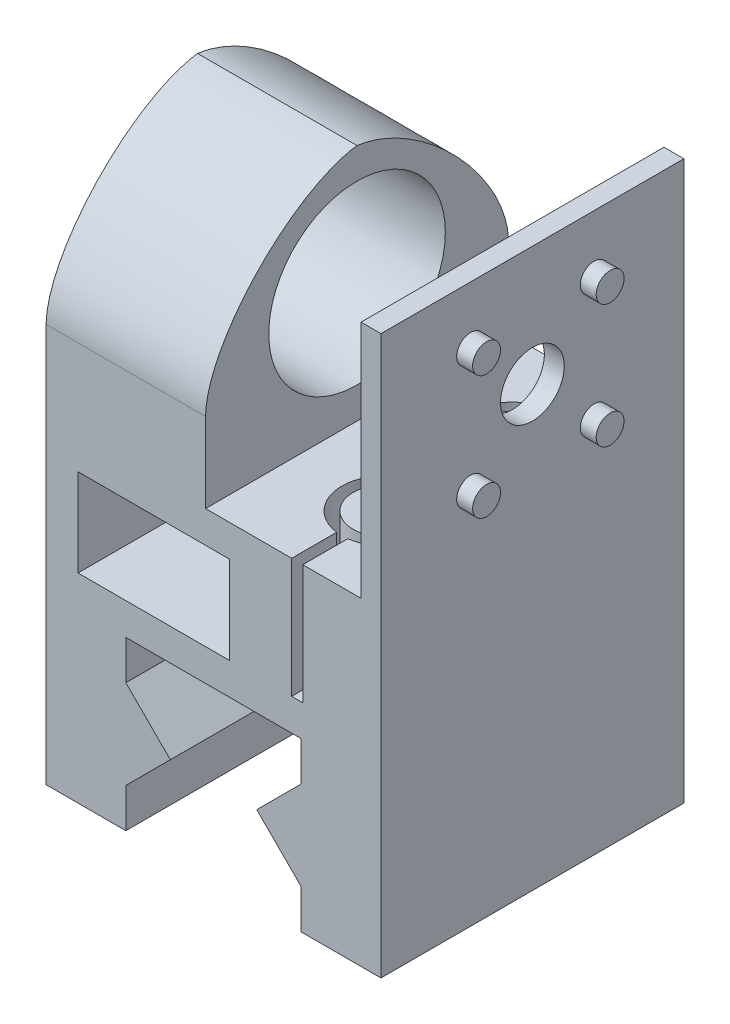
SolidWorks part; units mm, degrees
ref_plane "Front Plane" through (0, 0, 0) normal (0, 0, 1) x (1, 0, 0)
ref_plane "Top Plane" through (0, 0, 0) normal (0, 1, 0) x (1, 0, 0)
ref_plane "Right Plane" through (0, 0, 0) normal (1, 0, 0) x (0, 0, -1)
sketch "Sketch1" plane through (0, 0, 0) normal (0, 0, 1) x (1, 0, 0)
  line L0 (-11, 0) -> (11, 0)
  line L1 (11, 0) -> (11, -4.92)
  line L2 (11, -4.92) -> (5.42, -10.5)
  line L3 (5.42, -10.5) -> (11, -10.5) construction
  line L4 (11, -16.08) -> (5.42, -10.5)
  line L5 (11, -16.08) -> (11, -21)
  line L6 (0, 0) -> (0, -50000) construction
  line L7 (11, -21) -> (21, -21)
  line L8 (21, -21) -> (21, 19)
  line L9 (21, 19) -> (-21, 19)
  line L10 (-5.42, -10.5) -> (-11, -10.5) construction
  line L11 (-21, -21) -> (-21, 19)
  line L12 (-11, -21) -> (-21, -21)
  line L13 (-11, -16.08) -> (-11, -21)
  line L14 (-11, -16.08) -> (-5.42, -10.5)
  line L15 (-11, -4.92) -> (-5.42, -10.5)
  line L16 (-11, 0) -> (-11, -4.92)
  line L18 (-17, 15) -> (2, 15)
  line L19 (-17, 15) -> (-17, 4)
  line L20 (-17, 4) -> (2, 4)
  line L21 (2, 15) -> (2, 4)
  point P16 (0, 19)
  point P21 (0, 0)
  dimension "D1" = 11
  dimension "D2" = 4.92
  dimension "D3" = 7.8913
  dimension "D4" = 45
  dimension "D5" = 4.92
  dimension "D6" = 10
  dimension "D7" = 40
  dimension "D8" = 4
  dimension "D9" = 4
  dimension "D10" = 19
  dimension "D11" = 4
extrude "Boss-Extrude1" add sketch "Sketch1" along normal mid plane 38
sketch "Sketch2" plane through (0, 19, 0) normal (0, 1, 0) x (1, 0, 0)
  line L0 (21, -19) -> (-21, -19) construction
  line L1 (-21, 19) -> (-1, 19)
  line L2 (-21, 19) -> (-21, -19)
  line L3 (-21, -19) -> (-1, -19)
  line L4 (-1, 19) -> (-1, -19)
  dimension "D1" = 20
extrude "Boss-Extrude2" add sketch "Sketch2" along normal blind 30
fillet "Fillet2" radius 20 2 edges at (-11, 49, -19) (-11, 49, 19) conic rho 0.3
sketch "Sketch7" plane through (0, 19, 0) normal (0, 1, 0) x (1, 0, 0)
  line L0 (21, 19) -> (-1, 19) construction
  line L1 (18.5, 19) -> (21, 19)
  line L2 (18.5, 19) -> (18.5, -19)
  line L3 (18.5, -19) -> (21, -19)
  line L4 (21, 19) -> (21, -19)
  dimension "D1" = 2.5
extrude "Boss-Extrude6" add sketch "Sketch7" along normal blind 30
sketch "Sketch3" plane through (-21, 0, 0) normal (-1, 0, 0) x (0, 0, 1)
  line L0 (0, 0) -> (0, 44) construction
  circle A0 centre (0, 34) radius 11.075
  dimension "D1" = 22.15
  dimension "D2" = 34
extrude "Cut-Extrude1" cut sketch "Sketch3" against normal blind 31 and the other way through all
sketch "Sketch9" plane through (21, 0, 0) normal (1, 0, 0) x (0, 0, -1)
  line L0 (-19, 49) -> (19, 49) construction
  line L1 (-19, -21) -> (-19, 49) construction
  line L2 (19, -21) -> (19, 49) construction
  circle A0 centre (-7.75, 41.75) radius 1.75
  circle A1 centre (7.75, 41.75) radius 1.75
  circle A2 centre (-7.75, 26.25) radius 1.75
  circle A3 centre (7.75, 26.25) radius 1.75
  dimension "D1" = 3.5
  dimension "D2" = 3.5
  dimension "D3" = 3.5
  dimension "D4" = 3.5
  dimension "D5" = 7.25
  dimension "D6" = 11.25
  dimension "D7" = 11.25
  dimension "D8" = 15.5
extrude "Boss-Extrude7" add sketch "Sketch9" along normal blind 2
ref_axis "Axis1" through (-1, 34, 0) along (-1, 0, 0)
sketch "Sketch5" plane through (0, 19, 0) normal (0, 1, 0) x (1, 0, 0)
  line L0 (18.5, 19) -> (-1, 19) construction
  line L1 (18.5, 19) -> (21, 19)
  line L2 (18.5, 19) -> (18.5, -19)
  line L3 (18.5, -19) -> (21, -19)
  line L4 (21, 19) -> (21, -19)
  line L5 (18.5, -19) -> (-1, -19) construction
  line L6 (21, -19) -> (21, 19) construction
  dimension "D1" = 2.5
extrude "Boss-Extrude3" add sketch "Sketch5" along normal blind 30
sketch "Sketch8" plane through (21, 0, 0) normal (1, 0, 0) x (0, 0, -1)
  line L0 (-19, 49) -> (19, 49) construction
  circle A0 centre (0, 34) radius 4
  dimension "D1" = 15
  dimension "D2" = 8
extrude "Cut-Extrude4" cut sketch "Sketch8" against normal through all
sketch "Sketch11" plane through (0, 19, 0) normal (0, 1, 0) x (1, 0, 0)
  line L0 (0, 0) -> (21, 0) construction
  line L1 (21, -19) -> (21, 19) construction
  line L2 (10.5, 19) -> (10.5, -19) construction
  line L3 (9.8, -13.3544) -> (9.8, -19)
  line L4 (11.2, -13.3544) -> (11.2, -19)
  line L5 (9.8, 19) -> (9.8, 13.3544)
  line L6 (11.2, 19) -> (11.2, 13.3544)
  line L7 (9.8, 19) -> (11.2, 19)
  line L8 (9.8, -19) -> (11.2, -19)
  line L9 (11.2, 2.6456) -> (11.2, -2.6456)
  line L10 (9.8, 2.6456) -> (9.8, -2.6456)
  circle A0 centre (10.5, 8) radius 4
  circle A1 centre (10.5, -8) radius 4
  arc A2 (11.2, 2.6456) -> (11.2, 13.3544) centre (10.5, 8) ccw
  arc A3 (11.2, -13.3544) -> (11.2, -2.6456) centre (10.5, -8) ccw
  arc A4 (9.8, -2.6456) -> (9.8, -13.3544) centre (10.5, -8) ccw
  arc A5 (9.8, 13.3544) -> (9.8, 2.6456) centre (10.5, 8) ccw
  dimension "D7" = 8
  dimension "D8" = 10.8
  dimension "D9" = 10.8
  dimension "D1" = 38
  dimension "D2" = 1.4
  dimension "D3" = 9.8
  dimension "D4" = 19
  dimension "D5" = 8
  dimension "D6" = 8
extrude "Cut-Extrude5" cut sketch "Sketch11" against normal blind 15
